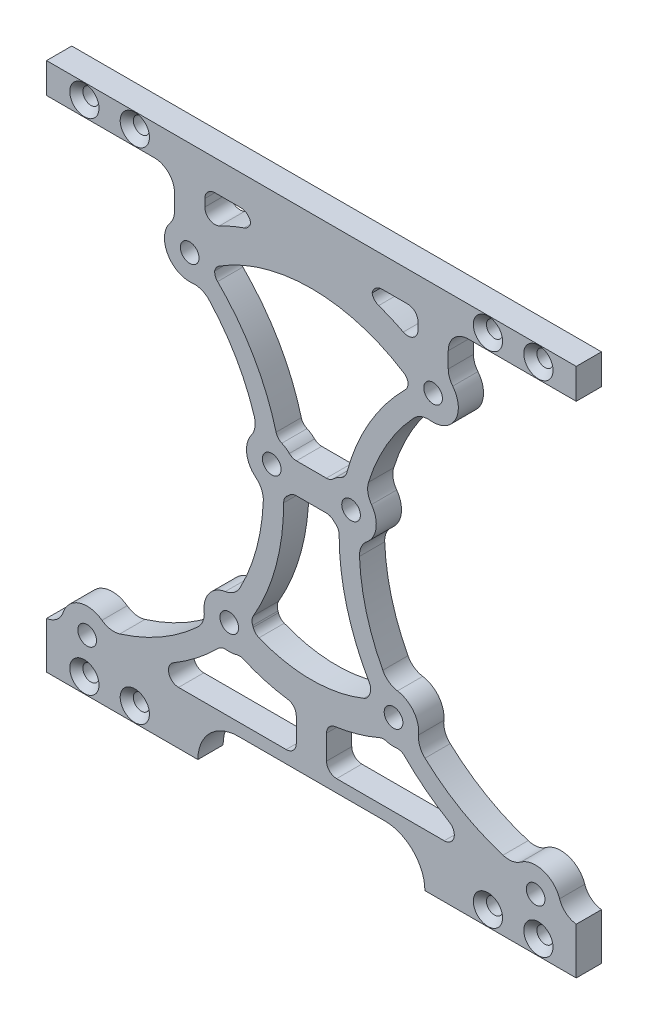
SolidWorks part; units mm, degrees
material "Thornel Mat VMA"
ref_plane "前视基准面" through (0, 0, 0) normal (0, 0, 1) x (1, 0, 0)
ref_plane "上视基准面" through (0, 0, 0) normal (0, 1, 0) x (1, 0, 0)
ref_plane "右视基准面" through (0, 0, 0) normal (1, 0, 0) x (0, 0, -1)
sketch "草图1" plane through (0, 0, 0) normal (0, 0, 1) x (1, 0, 0)
  line L1 (-50, 0) -> (-50, -42.5) construction
  line L2 (-55, 49.7494) -> (-55, 55)
  line L7 (-55, -49.7494) -> (-55, -55)
  line L8 (55, -55) -> (-55, -55)
  line L9 (-55, 55) -> (55, 55)
  line L10 (0, -55) -> (0, 55) construction
  line L11 (50, 0) -> (50, -42.5) construction
  line L12 (55, -49.7494) -> (55, -55)
  line L13 (55, 49.7494) -> (55, 55)
  arc A1 (-50, -42.5) -> (-44.4526, -42.1364) centre (-50, 0) ccw construction
  circle A2 centre (-44.4526, -42.1364) radius 1.85
  circle A3 centre (-75.8724, -33.7175) radius 1.85
  circle A4 centre (-92.1364, -5.5474) radius 1.85
  circle A5 centre (-83.7175, 25.8724) radius 1.85
  circle A6 centre (-55.5474, 42.1364) radius 1.85
  circle A7 centre (-24.1276, 33.7175) radius 1.85
  circle A8 centre (-7.8636, 5.5474) radius 1.85
  circle A9 centre (-16.2825, -25.8724) radius 1.85
  circle A10 centre (-50, 0) radius 37
  arc A11 (-55, 49.7494) -> (-55, -49.7494) centre (-50, 0) ccw
  arc A12 (50, -42.5) -> (44.4526, -42.1364) centre (50, 0) cw construction
  arc A13 (55, 49.7494) -> (55, -49.7494) centre (50, 0) cw
  circle A14 centre (50, 0) radius 37
  circle A15 centre (16.2825, -25.8724) radius 1.85
  circle A16 centre (7.8636, 5.5474) radius 1.85
  circle A17 centre (24.1276, 33.7175) radius 1.85
  circle A18 centre (55.5474, 42.1364) radius 1.85
  circle A19 centre (83.7175, 25.8724) radius 1.85
  circle A20 centre (92.1364, -5.5474) radius 1.85
  circle A21 centre (75.8724, -33.7175) radius 1.85
  circle A22 centre (44.4526, -42.1364) radius 1.85
  circle A25 centre (8, -47.5) radius 2.1
  circle A27 centre (-8, -47.5) radius 2.1
  point P23 (-50, 0)
  point P26 (50, 0)
  point P50 (0, 55)
  point P51 (0, -55)
  dimension "D1" = 8
extrude "凸台-拉伸1" add sketch "草图1" along normal blind 5
fillet "圆角1" radius 2.5 8 edges at (-55, -49.7494, 2.5) (-55, -55, 2.5) (55, -55, 2.5) (55, -49.7494, 2.5) (55, 49.7494, 2.5) (55, 55, 2.5) (-55, 55, 2.5) (-55, 49.7494, 2.5)
sketch "草图2" plane through (0, 0, 5) normal (0, 0, 1) x (1, 0, 0)
  line L0 (-52.5, 55) -> (-52.5, 52.5)
  line L1 (-52.5, 52.5) -> (52.5, 52.5)
  line L2 (55, 0) -> (-55, 0) construction
  line L3 (-52.5, -52.5) -> (52.5, -52.5)
  line L4 (-52.5, -55) -> (-52.5, -52.5)
  line L5 (0, -55) -> (0, 55) construction
  line L6 (52.5, -55) -> (52.5, -52.5)
  line L7 (52.5, 55) -> (52.5, 52.5)
  line L8 (-52.5, 55) -> (52.5, 55)
  line L9 (52.5, -55) -> (-52.5, -55)
  point P13 (0, -52.5)
  point P14 (0, 52.5)
extrude "切除-拉伸1" cut sketch "草图2" against normal blind 10
sketch "草图3" plane through (0, 0, 5) normal (0, 0, 1) x (1, 0, 0)
  line L0 (-52.5, 52.5) -> (-52.5, -52.5)
  line L1 (-52.5, -52.5) -> (52.5, -52.5)
  line L2 (52.5, -52.5) -> (52.5, 52.5)
  line L3 (52.5, 52.5) -> (-52.5, 52.5)
extrude "切除-拉伸2" cut sketch "草图3" against normal blind 10 flip side to cut
sketch "草图5" plane through (0, 0, 5) normal (0, 0, 1) x (1, 0, 0)
  line L0 (0, -2.75) -> (0, 2.75) construction
  line L2 (2.75, 0) -> (-2.75, 0) construction
  circle A2 centre (-45, 49.5) radius 1.6
  circle A5 centre (-35, 49.5) radius 1.6
  circle A6 centre (35, 49.5) radius 1.6
  circle A7 centre (45, 49.5) radius 1.6
  circle A8 centre (45, -49.5) radius 1.6
  circle A9 centre (35, -49.5) radius 1.6
  circle A10 centre (-35, -49.5) radius 1.6
  circle A11 centre (-45, -49.5) radius 1.6
extrude "切除-拉伸3" cut sketch "草图5" against normal blind 10
sketch "草图6" plane through (0, 0, 5) normal (0, 0, 1) x (1, 0, 0)
  line L2 (-52.5, 52.5) -> (-52.5, 36.9154) construction
  line L4 (-3.8636, 2.5474) -> (3.8636, 2.5474)
  line L5 (-3.8636, 8.5474) -> (3.8636, 8.5474)
  line L8 (0, -2.75) -> (0, 2.75) construction
  line L9 (-52.5, 46.5) -> (-52.5, 52.5)
  line L13 (-52.5, 52.5) -> (52.5, 52.5) construction
  line L16 (-52.5, 52.5) -> (52.5, 52.5)
  line L19 (-27.1276, 46.5) -> (-52.5, 46.5)
  line L20 (21.1276, 46.5) -> (21.1276, 39.6188)
  line L21 (-27.1276, 37.7175) -> (-27.1276, 46.5)
  line L22 (-21.1276, 46.5) -> (-21.1276, 39.6188)
  line L23 (27.1276, 37.7175) -> (27.1276, 46.5)
  line L24 (52.5, 46.5) -> (27.1276, 46.5)
  line L25 (52.5, 46.5) -> (52.5, 52.5)
  line L26 (-12, 46.5) -> (-21.1276, 46.5)
  line L27 (-12, 46.5) -> (-12, 43.7997)
  line L28 (12, 46.5) -> (12, 43.7997)
  line L29 (12, 46.5) -> (21.1276, 46.5)
  line L31 (-52.5, -43.2631) -> (-52.5, -52.5)
  line L32 (52.5, -52.5) -> (52.5, -36.9154) construction
  line L33 (49.3363, -43.2089) -> (52.5, -43.2631)
  line L34 (52.5, -43.2631) -> (52.5, -52.5)
  line L35 (52.5, -52.5) -> (-52.5, -52.5)
  line L36 (52.5, -52.5) -> (-52.5, -52.5) construction
  line L37 (-49.3363, -43.2089) -> (-52.5, -43.2631)
  line L39 (3, -42.0254) -> (3, -33.4352)
  line L40 (-3, -42.0254) -> (-3, -33.4352)
  line L47 (-3, -42.0254) -> (-35.3674, -42.0254)
  line L48 (3, -42.0254) -> (35.3674, -42.0254)
  arc A1 (-5.5144, 1.1336) -> (-3.8636, 2.5474) centre (-7.8636, 5.5474) ccw
  arc A3 (-15.3461, -20.9608) -> (-20.7843, -28.048) centre (-16.2825, -25.8724) ccw
  arc A5 (-40.3175, -39.3256) -> (-20.7843, -28.048) centre (-50, 0) ccw
  arc A6 (-35.3674, -42.0254) -> (-17.7424, -30.6545) centre (-50, 0) ccw
  arc A8 (-10.6744, 9.6825) -> (-9.5084, 0.8257) centre (-7.8636, 5.5474) ccw
  arc A9 (-10.6744, 9.6825) -> (-21.952, 29.2157) centre (-50, 0) ccw
  arc A10 (-6.7369, 10.4188) -> (-19.3455, 32.2576) centre (-50, 0) ccw
  arc A11 (-15.3461, -20.9608) -> (-9.5084, 0.8257) centre (-50, 0) ccw
  arc A12 (-12.0412, -23.2245) -> (-5.5144, 1.1336) centre (-50, 0) ccw
  arc A13 (-17.7424, -30.6545) -> (-14.2003, -30.4182) centre (-16.2825, -25.8724) ccw
  arc A14 (-3.8636, 8.5474) -> (-6.7369, 10.4188) centre (-7.8636, 5.5474) ccw
  arc A16 (19.1279, 33.7658) -> (-19.1279, 33.7658) centre (0, 5.5474) ccw
  arc A17 (-12, 43.7997) -> (-21.1276, 39.6188) centre (0, 5.5474) ccw
  arc A20 (3.8636, 8.5474) -> (6.7369, 10.4188) centre (7.8636, 5.5474) cw
  arc A21 (17.7424, -30.6545) -> (14.2003, -30.4182) centre (16.2825, -25.8724) cw
  arc A22 (12.0412, -23.2245) -> (5.5144, 1.1336) centre (50, 0) cw
  arc A23 (15.3461, -20.9608) -> (9.5084, 0.8257) centre (50, 0) cw
  arc A24 (6.7369, 10.4188) -> (19.3455, 32.2576) centre (50, 0) cw
  arc A25 (10.6744, 9.6825) -> (21.952, 29.2157) centre (50, 0) cw
  arc A26 (10.6744, 9.6825) -> (9.5084, 0.8257) centre (7.8636, 5.5474) cw
  arc A28 (35.3674, -42.0254) -> (17.7424, -30.6545) centre (50, 0) cw
  arc A29 (40.3175, -39.3256) -> (20.7843, -28.048) centre (50, 0) cw
  arc A30 (15.3461, -20.9608) -> (20.7843, -28.048) centre (16.2825, -25.8724) cw
  arc A31 (40.3175, -39.3256) -> (49.3363, -43.2089) centre (44.4526, -42.1364) cw
  arc A32 (5.5144, 1.1336) -> (3.8636, 2.5474) centre (7.8636, 5.5474) cw
  arc A34 (-19.3455, 32.2576) -> (-19.1279, 33.7658) centre (-24.1276, 33.7175) ccw
  arc A35 (-27.1276, 37.7175) -> (-21.952, 29.2157) centre (-24.1276, 33.7175) ccw
  arc A36 (27.1276, 37.7175) -> (21.952, 29.2157) centre (24.1276, 33.7175) cw
  arc A37 (19.3455, 32.2576) -> (19.1279, 33.7658) centre (24.1276, 33.7175) cw
  arc A38 (12, 43.7997) -> (21.1276, 39.6188) centre (0, 5.5474) cw
  arc A39 (-40.3175, -39.3256) -> (-49.3363, -43.2089) centre (-44.4526, -42.1364) ccw
  arc A40 (3, -33.4352) -> (14.2003, -30.4182) centre (0, 0) ccw
  arc A42 (-14.2003, -30.4182) -> (-3, -33.4352) centre (0, 0) ccw
  arc A43 (-11.3378, -25.1303) -> (11.3378, -25.1303) centre (0, 0) ccw
  arc A44 (-11.3378, -25.1303) -> (-12.0412, -23.2245) centre (-16.2825, -25.8724) ccw
  arc A48 (11.3378, -25.1303) -> (12.0412, -23.2245) centre (16.2825, -25.8724) cw
  point P15 (0, 0)
  point P23 (-7.8636, 2.5474)
  point P26 (7.8636, 2.5474)
  point P27 (-7.8636, 8.5474)
  point P33 (7.8636, 8.5474)
  point P39 (-24.9781, 40.0639)
  point P41 (0, 2.5474)
  point P46 (-35.8957, 50.5)
  point P50 (-21.1276, 33.7175)
  point P70 (-38.6395, -43.0254)
  point P76 (0, 52.5)
  point P77 (0, 46.5)
  point P78 (0, 8.5474)
  point P80 (-27.1276, 33.7175)
  point P81 (0, -52.5)
  point P97 (0, -43.0254)
  point P100 (14.6876, -26.8099)
  point P103 (0, -43.0254)
  point P105 (-17.8804, -28.4114)
  point P106 (16.129, -29.441)
  point P108 (-14.6846, -23.3333)
  point P109 (13.2462, -24.1789)
  point P113 (0, -31.1409)
  point P115 (3, -43.0254)
  point P116 (3, -31.1409)
  point P117 (-3, -43.0254)
  point P118 (-3, -31.1409)
extrude "切除-拉伸4" cut sketch "草图6" against normal blind 10 flip side to cut
fillet "圆角2" radius 4 18 edges at (27.1276, 46.5, 2.5) (27.1276, 37.7175, 2.5) (21.952, 29.2157, 2.5) (10.6744, 9.6825, 2.5) (9.5084, 0.8257, 2.5) (15.3461, -20.9608, 2.5) (20.7843, -28.048, 2.5) (40.3175, -39.3256, 2.5) (49.3363, -43.2089, 2.5) (-27.1276, 46.5, 2.5) (-27.1276, 37.7175, 2.5) (-21.952, 29.2157, 2.5) (-9.5084, 0.8257, 2.5) (-10.6744, 9.6825, 2.5) (-49.3363, -43.2089, 2.5) (-40.3175, -39.3256, 2.5) (-20.7843, -28.048, 2.5) (-15.3461, -20.9608, 2.5)
fillet "圆角3" radius 2 34 edges at (21.1276, 46.5, 2.5) (12, 46.5, 2.5) (12, 43.7997, 2.5) (21.1276, 39.6188, 2.5) (19.3455, 32.2576, 2.5) (19.1279, 33.7658, 2.5) (6.7369, 10.4188, 2.5) (3.8636, 8.5474, 2.5) (3.8636, 2.5474, 2.5) (5.5144, 1.1336, 2.5) (11.3378, -25.1303, 2.5) (12.0412, -23.2245, 2.5) (17.7424, -30.6545, 2.5) (14.2003, -30.4182, 2.5) (3, -33.4352, 2.5) (3, -42.0254, 2.5) (35.3674, -42.0254, 2.5) (-35.3674, -42.0254, 2.5) (-3, -42.0254, 2.5) (-3, -33.4352, 2.5) (-14.2003, -30.4182, 2.5) (-17.7424, -30.6545, 2.5) (-11.3378, -25.1303, 2.5) (-12.0412, -23.2245, 2.5) (-5.5144, 1.1336, 2.5) (-3.8636, 2.5474, 2.5) (-19.3455, 32.2576, 2.5) (-19.1279, 33.7658, 2.5) (-3.8636, 8.5474, 2.5) (-6.7369, 10.4188, 2.5) (-21.1276, 46.5, 2.5) (-21.1276, 39.6188, 2.5) (-12, 46.5, 2.5) (-12, 43.7997, 2.5)
sketch "草图7" plane through (0, 0, 5) normal (0, 0, 1) x (1, 0, 0)
  line L0 (-52.5, -52.5) -> (-22.5, -52.5)
  line L1 (52.5, -52.5) -> (-52.5, -52.5) construction
  line L2 (-14.5, -44.5) -> (14.5, -44.5)
  line L3 (-22.5, -52.5) -> (22.5, -52.5)
  line L4 (0, -2.75) -> (0, 2.75) construction
  line L5 (52.5, -52.5) -> (22.5, -52.5)
  arc A0 (22.5, -52.5) -> (14.5, -44.5) centre (14.5, -52.5) ccw
  arc A1 (-22.5, -52.5) -> (-14.5, -44.5) centre (-14.5, -52.5) cw
  point P6 (0, -44.5)
  point P14 (0, -52.5)
extrude "切除-拉伸5" cut sketch "草图7" against normal blind 10 contours A1 L3 A0 L2 region at (0, -48.6828, 5)
chamfer "倒角1" distance 1.3 angle 45 8 edges at (43.4, 49.5, 5) (33.4, 49.5, 5) (-33.4, 49.5, 5) (-43.4, 49.5, 5) (46.6, -49.5, 5) (36.6, -49.5, 5) (-36.6, -49.5, 5) (-46.6, -49.5, 5)
